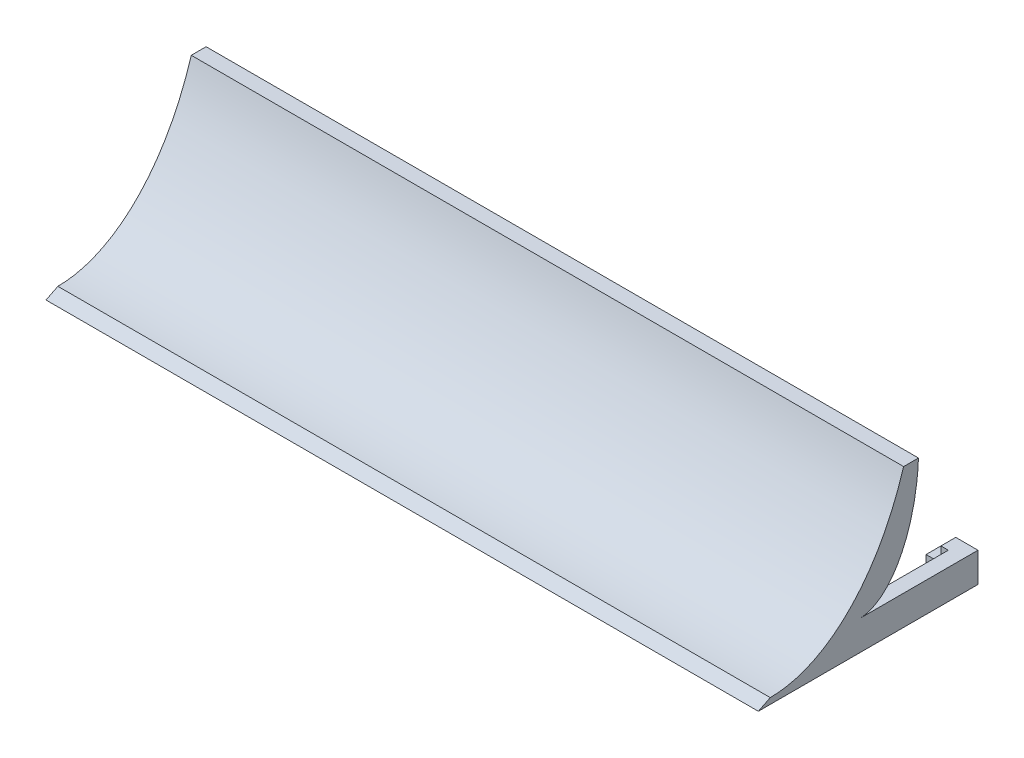
SolidWorks part; units mm, degrees
ref_plane "Alzado" through (0, 0, 0) normal (0, 0, 1) x (1, 0, 0)
ref_plane "Planta" through (0, 0, 0) normal (0, 1, 0) x (1, 0, 0)
ref_plane "Vista lateral" through (0, 0, 0) normal (1, 0, 0) x (0, 0, -1)
sketch "Croquis4" plane through (0, 0, 0) normal (1, 0, 0) x (0, 0, -1)
  line L0 (33.8376, 0) -> (-70.9068, 0) construction
  line L1 (0, -18.282) -> (0, 71.3339) construction
  line L2 (9.9706, 23.4676) -> (7.4706, 23.4676)
  line L4 (0, 0) -> (0, 5)
  line L7 (-15, 1) -> (-15, 81) construction
  line L8 (0, 0) -> (-17, 0)
  line L9 (-15, 1) -> (-17, 0)
  ellipse E0 centre (0, 25) end of major axis (0, 5) minor radius 10 (0, 5) -> (9.9706, 23.4676) ccw
  ellipse E1 centre (-15, 41) end of major axis (-15, 1) minor radius 25 (-15, 1) -> (7.4706, 23.4676) ccw
  point P6 (0, 0)
  point P19 (-16.706, 0)
  dimension "D1" = 2
  dimension "D3" = 10
  dimension "D4" = 20
  dimension "D5" = 40
  dimension "D6" = 25
  dimension "D7" = 1
  dimension "D8" = 15
  dimension "D9" = 2.5
extrude "Cuchilla-Saliente" add sketch "Croquis4" along normal blind 60 and the other way blind 60
sketch "Encaje-Cuchilla-Lateral-Croquis-1" plane through (60, 0, 0) normal (1, 0, 0) x (0, 0, -1)
  line L1 (0, 0) -> (20, 0)
  line L2 (0, 0) -> (0, 5)
  line L3 (0, 5) -> (20, 5)
  line L4 (20, 0) -> (20, 5)
  dimension "D1" = 20
extrude "Encaje-Cuchilla-Lateral-Saliente-1" add sketch "Encaje-Cuchilla-Lateral-Croquis-1" against normal blind 2.5
sketch "Encaje-Cuchilla-Lateral-Croquis-2" plane through (57.5, 0, 0) normal (-1, 0, 0) x (0, 0, 1)
  line L0 (-20, 0) -> (-20, 5) construction
  line L1 (0, 0) -> (-20, 0)
  line L2 (0, 0) -> (0, 2.5)
  line L3 (0, 2.5) -> (-20, 2.5)
  line L4 (-20, 0) -> (-20, 2.5)
extrude "Encaje-Cuchilla-Lateral-Saliente-2" add sketch "Encaje-Cuchilla-Lateral-Croquis-2" along normal blind 2.5
sketch "Encaje-Cuchilla-Lateral-Croquis-3" plane through (55, 0, 0) normal (-1, 0, 0) x (0, 0, 1)
  line L1 (-20, 2.5) -> (-17.5, 2.5)
  line L2 (-20, 2.5) -> (-20, 1.25)
  line L3 (-20, 1.25) -> (-17.5, 1.25)
  line L4 (-17.5, 2.5) -> (-17.5, 1.25)
  dimension "D1" = 2.5
extrude "Encaje-Cuchilla-Lateral-Saliente-3" add sketch "Encaje-Cuchilla-Lateral-Croquis-3" along normal blind 1.25
sketch "Encaje-Cuchilla-Lateral-Croquis-4" plane through (57.5, 0, 0) normal (-1, 0, 0) x (0, 0, 1)
  line L1 (-20, 5) -> (-17.5, 5)
  line L2 (-20, 5) -> (-20, 3.75)
  line L3 (-20, 3.75) -> (-17.5, 3.75)
  line L4 (-17.5, 5) -> (-17.5, 3.75)
  dimension "D1" = 2.5
  dimension "D2" = 1.25
extrude "Encaje-Cuchilla-Lateral-Saliente-4" add sketch "Encaje-Cuchilla-Lateral-Croquis-4" along normal blind 1.25 contours L2 L1 L4 L3
sketch "Encaje-Cuchilla-Lateral-Croquis-5" plane through (-60, 0, 0) normal (-1, 0, 0) x (0, 0, 1)
  line L1 (0, 0) -> (-20, 0)
  line L2 (0, 0) -> (0, 5)
  line L3 (0, 5) -> (-20, 5)
  line L4 (-20, 0) -> (-20, 5)
extrude "Encaje-Cuchilla-Lateral-Saliente-5" add sketch "Encaje-Cuchilla-Lateral-Croquis-5" against normal blind 2.5 separate body
sketch "Encaje-Cuchilla-Lateral-Croquis-6" plane through (-57.5, 0, 0) normal (1, 0, 0) x (0, 0, -1)
  line L1 (20, 0) -> (0, 0)
  line L2 (20, 0) -> (20, 2.5)
  line L3 (20, 2.5) -> (0, 2.5)
  line L4 (0, 0) -> (0, 2.5)
extrude "Encaje-Cuchilla-Lateral-Saliente-6" add sketch "Encaje-Cuchilla-Lateral-Croquis-6" along normal blind 2.5
sketch "Encaje-Cuchilla-Lateral-Croquis-7" plane through (-57.5, 0, 0) normal (1, 0, 0) x (0, 0, -1)
  line L1 (20, 5) -> (17.5, 5)
  line L2 (20, 5) -> (20, 3.75)
  line L3 (20, 3.75) -> (17.5, 3.75)
  line L4 (17.5, 5) -> (17.5, 3.75)
  dimension "D1" = 2.5
  dimension "D2" = 1.25
extrude "Encaje-Cuchilla-Lateral-Saliente-7" add sketch "Encaje-Cuchilla-Lateral-Croquis-7" along normal blind 1.25
sketch "Encaje-Cuchilla-Lateral-Croquis-8" plane through (-55, 0, 0) normal (1, 0, 0) x (0, 0, -1)
  line L0 (20, 0) -> (20, 5) construction
  line L1 (20, 2.5) -> (17.5, 2.5)
  line L2 (20, 2.5) -> (20, 1.25)
  line L3 (20, 1.25) -> (17.5, 1.25)
  line L4 (17.5, 2.5) -> (17.5, 1.25)
  dimension "D1" = 2.5
  dimension "D2" = 1.25
extrude "Encaje-Cuchilla-Lateral-Saliente-8" add sketch "Encaje-Cuchilla-Lateral-Croquis-8" along normal blind 1.25
sketch "Encaje-Cuchilla-Central-Croquis" plane through (0, 0, 0) normal (0, 0, -1) x (-1, 0, 0)
  line L0 (0, 0) -> (0, 5) construction
  line L1 (55, 0) -> (-55, 0) construction
  line L2 (57.5, 5) -> (-57.5, 5) construction
  line L3 (2.5, 3.125) -> (5, 3.125)
  line L4 (2.5, 0) -> (-2.5, 0)
  line L5 (2.5, 0) -> (2.5, 1.875)
  line L6 (2.5, 5) -> (-2.5, 5)
  line L7 (-2.5, 0) -> (-2.5, 1.875)
  line L8 (2.5, 0) -> (-2.5, 5) construction
  line L9 (2.5, 5) -> (-2.5, 0) construction
  line L10 (-5, 1.875) -> (-2.5, 1.875)
  line L11 (-5, 1.875) -> (-5, 3.125)
  line L12 (-5, 3.125) -> (-2.5, 3.125)
  line L13 (5, 1.875) -> (5, 3.125)
  line L14 (-5, 1.875) -> (5, 3.125) construction
  line L15 (-5, 3.125) -> (5, 1.875) construction
  line L16 (-2.5, 3.125) -> (-2.5, 5)
  line L17 (2.5, 3.125) -> (2.5, 5)
  line L18 (2.5, 1.875) -> (5, 1.875)
  point P6 (0, 2.5)
  point P11 (0, 2.5)
  dimension "D1" = 5
  dimension "D2" = 10
  dimension "D3" = 1.25
extrude "Encaje-Cuchilla-Central-Saliente" add sketch "Encaje-Cuchilla-Central-Croquis" along normal blind 20
